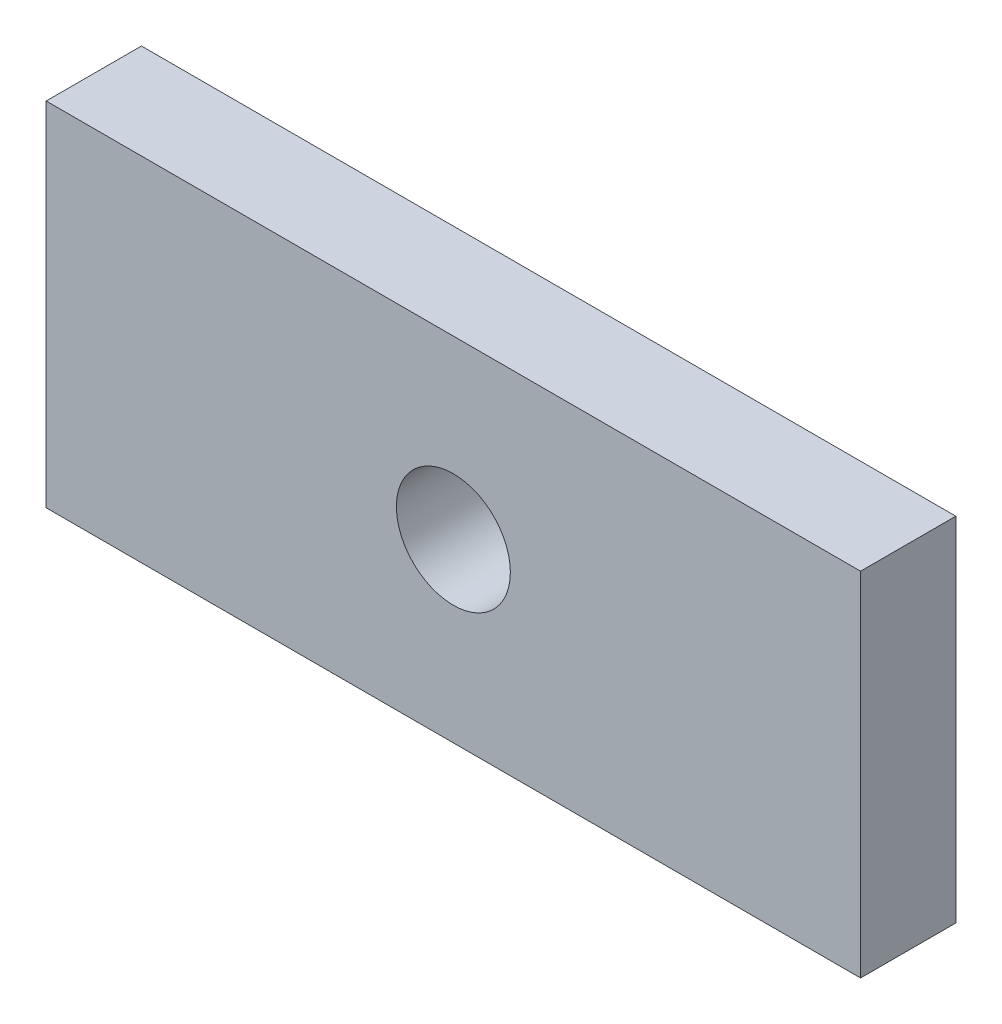
SolidWorks part; units mm, degrees
ref_plane "Front Plane" through (0, 0, 0) normal (1, 0, 0) x (0, 1, 0)
ref_plane "Top Plane" through (0, 0, 0) normal (0, 0, 1) x (0, 1, 0)
ref_plane "Right Plane" through (0, 0, 0) normal (0, 1, 0) x (-1, 0, 0)
sketch "Sketch1" plane through (0, 0, 0) normal (0, 0, 1) x (0, 1, 0)
  line L1 (-18.4943, -42.749) -> (18.4943, -42.749)
  line L2 (-18.4943, -42.749) -> (-18.4943, 42.749)
  line L3 (-18.4943, 42.749) -> (18.4943, 42.749)
  line L4 (18.4943, -42.749) -> (18.4943, 42.749)
  line L5 (-18.4943, -42.749) -> (18.4943, 42.749) construction
  line L6 (-18.4943, 42.749) -> (18.4943, -42.749) construction
  point P0 (0, 0)
extrude "Boss-Extrude1" add sketch "Sketch1" along normal blind 10
sketch "Sketch2" plane through (0, 0, 10) normal (0, 0, 1) x (1, 0, 0)
  circle A0 centre (0, 0) radius 5.9812
extrude "Cut-Extrude1" cut sketch "Sketch2" against normal blind 10
